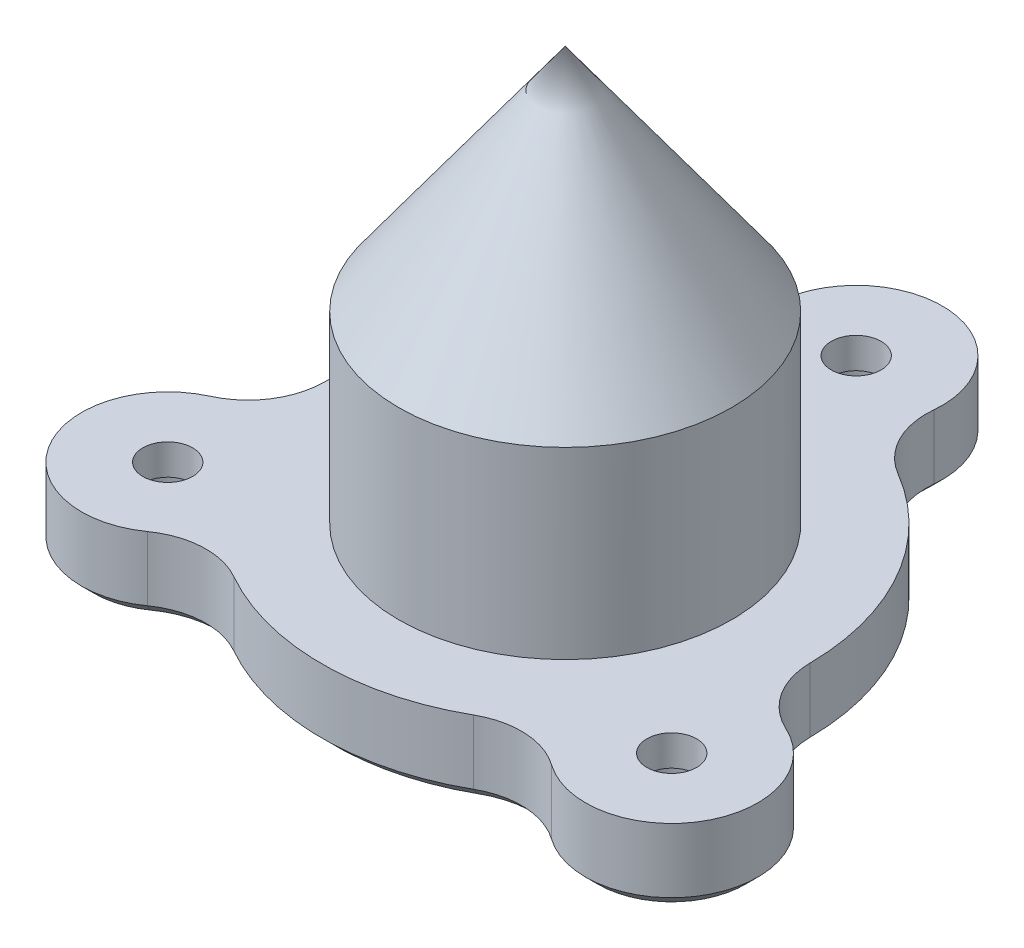
SolidWorks part; units mm, degrees
ref_plane "Front Plane" through (0, 0, 0) normal (0, 0, 1) x (1, 0, 0)
ref_plane "Top Plane" through (0, 0, 0) normal (0, 1, 0) x (1, 0, 0)
ref_plane "Right Plane" through (0, 0, 0) normal (1, 0, 0) x (0, 0, -1)
sketch "Sketch1" plane through (0, 0, 0) normal (0, 1, 0) x (1, 0, 0)
  line L0 (0, 0) -> (0, 32.0938) construction
  line L1 (0, 19) -> (7.7655, 19) construction
  circle A0 centre (0, 0) radius 10.875
  circle A1 centre (0, 19) radius 1.625
  arc A6 (5.5999, 18.4688) -> (-5.5999, 18.4688) centre (0, 19) ccw
  arc A7 (-8.044, 13.6861) -> (-15.8745, 0.1232) centre (0, 0) ccw
  arc A10 (5.5999, 18.4688) -> (8.044, 13.6861) centre (10.5775, 17.9967) ccw
  arc A11 (-5.5999, 18.4688) -> (-8.044, 13.6861) centre (-10.5775, 17.9967) cw
  circle A12 centre (0, 19) radius 5.625 construction
  arc A13 (13.1946, -14.084) -> (18.7944, -4.3848) centre (16.4545, -9.5) ccw
  circle A14 centre (0, 0) radius 15.875 construction
  circle A15 centre (16.4545, -9.5) radius 1.625
  arc A16 (13.1946, -14.084) -> (7.8305, -13.8094) centre (10.2968, -18.1588) ccw
  arc A17 (18.7944, -4.3848) -> (15.8745, 0.1232) centre (20.8744, 0.1621) cw
  arc A18 (-18.7944, -4.3848) -> (-13.1946, -14.084) centre (-16.4545, -9.5) ccw
  circle A19 centre (-16.4545, -9.5) radius 1.625
  arc A20 (-18.7944, -4.3848) -> (-15.8745, 0.1232) centre (-20.8744, 0.1621) ccw
  arc A21 (-13.1946, -14.084) -> (-7.8305, -13.8094) centre (-10.2968, -18.1588) cw
  arc A22 (15.8745, 0.1232) -> (8.044, 13.6861) centre (0, 0) ccw
  arc A23 (-7.8305, -13.8094) -> (7.8305, -13.8094) centre (0, 0) ccw
  point P13 (0, 0)
  point P15 (4.3, 19)
  point P17 (15, 0)
  point P41 (0, 0)
  dimension "D1" = 21.75
  dimension "D3" = 3.25
  dimension "D4" = 10
  dimension "D2" = 19
  dimension "D5" = 5
  dimension "D6" = 4
  dimension "D7" = 3
extrude "Boss-Extrude1" add sketch "Sketch1" along normal blind 5
extrude "Boss-Extrude2" add sketch "Sketch1<2>" along normal blind 17 contours A0 region at (0, 0, 0)
sketch "Sketch1<2>" plane through (0, 0, 0) normal (0, 1, 0) x (1, 0, 0) same geometry as "Sketch1"
sketch "Sketch2" plane through (0, 0, 0) normal (0, 0, 1) x (1, 0, 0)
  line L0 (0, 18.4135) -> (0, 7.4654) construction
  line L1 (0, 17) -> (10.875, 17)
  line L2 (10.875, 17) -> (-10.875, 17) construction
  line L3 (10.875, 17) -> (0, 32)
  line L4 (0, 32) -> (0, 17)
  dimension "D1" = 15
revolve "Revolve1" add sketch "Sketch2" angle 360 about L0
chamfer "Chamfer1" distance 0.8 angle 45 12 edges at (0, 0, -24.625) (-6.1252, 0, -15.7214) (6.1252, 0, -15.7214) (-13.7482, 0, -7.9375) (13.7482, 0, -7.9375) (-16.6778, 0, 2.5561) (16.6778, 0, 2.5561) (-21.3259, 0, 12.3125) (21.3259, 0, 12.3125) (-10.5526, 0, 13.1653) (10.5526, 0, 13.1653) (0, 0, 15.875)
sketch "Sketch3" plane through (0, 0, 0) normal (0, -1, 0) x (1, 0, 0)
  line L0 (0, 0) -> (0, -24.6565) construction
  circle A0 centre (0, -19) radius 2.875
  circle A1 centre (-16.4545, 9.5) radius 2.875
  circle A2 centre (16.4545, 9.5) radius 2.875
  point P13 (0, 0)
  dimension "D1" = 5.75
  dimension "D2" = 3
extrude "Cut-Extrude1" cut sketch "Sketch3" against normal blind 3
chamfer "Chamfer2" distance 0.4 angle 45 3 edges at (0, 0, -21.875) (16.4545, 0, 6.625) (-16.4545, 0, 6.625)
